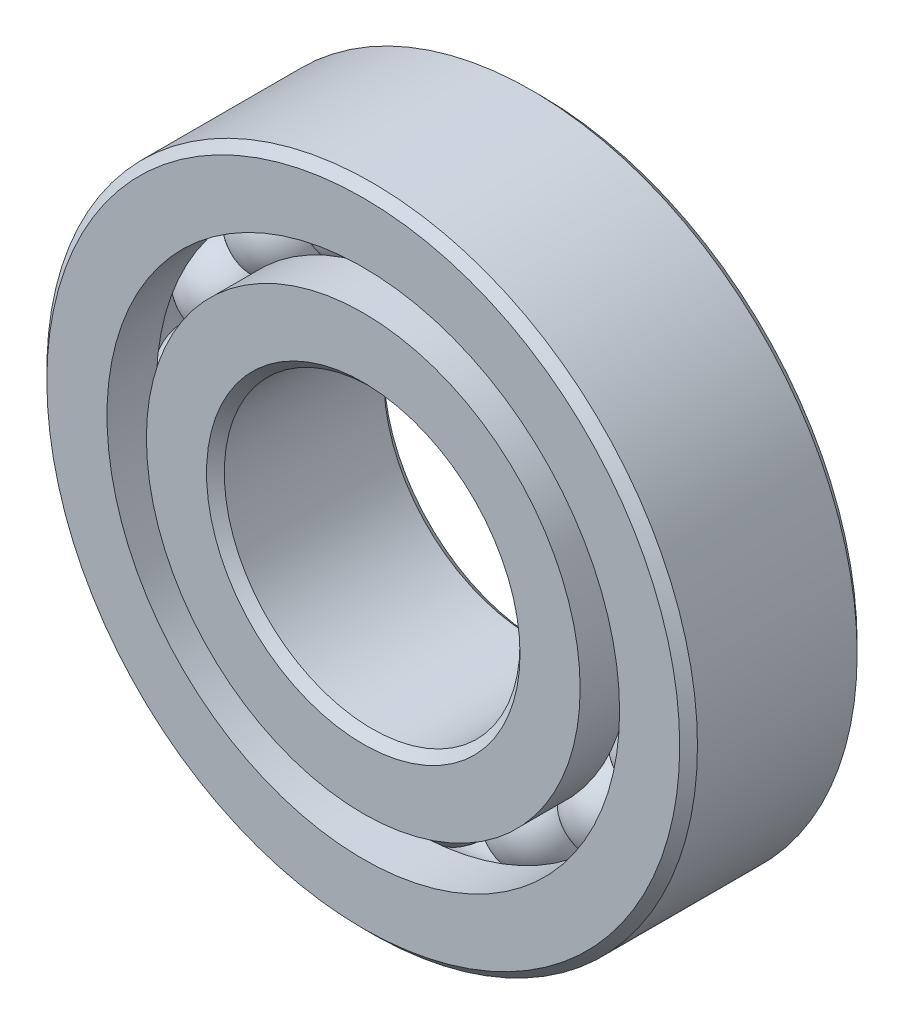
SolidWorks part; units mm, degrees
ref_plane "Front Plane" through (0, 0, 0) normal (0, 0, 1) x (1, 0, 0)
ref_plane "Top Plane" through (0, 0, 0) normal (0, 1, 0) x (1, 0, 0)
ref_plane "Right Plane" through (0, 0, 0) normal (1, 0, 0) x (0, 0, -1)
sketch "Sketch1" plane through (0, 0, 0) normal (1, 0, 0) x (0, 0, -1)
  line L0 (-1.5, 0) -> (1.5, 0) construction
  line L1 (0, 5.5) -> (0, -5.5) construction
  line L2 (1.35, 5.5) -> (-1.35, 5.5) construction
  line L3 (-1.35, 5.5) -> (-1.5, 5.35) construction
  line L4 (-1.5, 5.35) -> (-1.5, 4.3333) construction
  line L5 (-1.5, 4.3333) -> (-0.6667, 4.3333) construction
  line L6 (1.5, 4.3333) -> (0.6667, 4.3333) construction
  line L7 (1.5, 5.35) -> (1.5, 4.3333) construction
  line L8 (1.35, 5.5) -> (1.5, 5.35) construction
  line L9 (0, 5.5) -> (0, 4) construction
  line L10 (0, 4) -> (0, 2.5) construction
  arc A0 (-0.6667, 4.3333) -> (0.6667, 4.3333) centre (0, 4) cw construction
  arc A1 (-0.6667, 4.3333) -> (0.6667, 4.3333) centre (0, 4) ccw construction
  point P14 (0, 2.5)
  point P15 (0, -2.5)
  dimension "Width" = 3
  dimension "OD" = 11
  dimension "D1" = 45
  dimension "D2" = 0.15
  dimension "D3" = 1.3333
  dimension "Shaft Dia" = 5
  dimension "D4" = 0.3333
sketch "Sketch2" plane through (0, 0, 0) normal (1, 0, 0) x (0, 0, -1)
  line L0 (-1.5, 3.6667) -> (-0.6667, 3.6667)
  line L2 (-1.5, 3.6667) -> (-1.5, 2.65)
  line L3 (-1.5, 2.65) -> (-1.35, 2.5)
  line L4 (-1.35, 2.5) -> (1.35, 2.5)
  line L5 (0, 5.5) -> (0, -5.5) construction
  line L6 (0, 2.5) -> (0, 3.2546) construction
  line L7 (0, 3.2546) -> (0, 2.5) construction
  line L9 (-1.5, 5.35) -> (-1.5, 4.3333) construction
  line L10 (1.5, 3.6667) -> (0.6667, 3.6667)
  line L11 (1.5, 3.6667) -> (1.5, 2.65)
  line L12 (1.5, 2.65) -> (1.35, 2.5)
  line L13 (1.35, 5.5) -> (1.5, 5.35) construction
  line L14 (1.5, 5.35) -> (1.5, 4.3333) construction
  line L15 (1.5, 4.3333) -> (0.6667, 4.3333) construction
  line L16 (-1.5, 4.3333) -> (-0.6667, 4.3333) construction
  line L17 (1.35, 5.5) -> (-1.35, 5.5) construction
  line L18 (-1.35, 5.5) -> (-1.5, 5.35) construction
  line L19 (1.35, 5.5) -> (1.5, 5.35)
  line L20 (1.5, 5.35) -> (1.5, 4.3333)
  line L21 (1.5, 4.3333) -> (0.6667, 4.3333)
  line L22 (-1.5, 4.3333) -> (-0.6667, 4.3333)
  line L23 (-1.5, 5.35) -> (-1.5, 4.3333)
  line L24 (1.35, 5.5) -> (-1.35, 5.5)
  line L25 (-1.35, 5.5) -> (-1.5, 5.35)
  line L26 (-1.5, 2.65) -> (-1.35, 2.65) construction
  line L27 (-1.35, 2.65) -> (-1.35, 2.5) construction
  arc A0 (-0.6667, 3.6667) -> (0.6667, 3.6667) centre (0, 4) ccw
  arc A1 (0.6667, 4.3333) -> (-0.6667, 4.3333) centre (0, 4) ccw construction
  circle A2 centre (0, 4) radius 0.7454 construction
  arc A3 (-0.6667, 4.3333) -> (0.6667, 4.3333) centre (0, 4) cw
  dimension "D1" = 0.15
revolve "Revolve1" add sketch "Sketch2" angle 360 about L0
sketch "Sketch3" plane through (0, 0, 0) normal (1, 0, 0) x (0, 0, -1)
  line L0 (-0.7454, 4) -> (0.7454, 4)
  line L1 (0, 4) -> (0, 0) construction
  circle A1 centre (0, 4) radius 0.7454 construction
  arc A2 (-0.7454, 4) -> (0.7454, 4) centre (0, 4) cw
  arc A3 (0.6667, 4.3333) -> (-0.6667, 4.3333) centre (0, 4) ccw construction
  dimension "D1" = 1.4907
  dimension "D2" = 4
revolve "Revolve2" add sketch "Sketch3" angle 360 about L0
ref_axis "Axis1" through (0, 0, -1.5) along (0, 0, 1)
pattern_circular "CirPattern1" count 16 every 22.5 about axis through (0, 0, -1.5) along (0, 0, 1) of bodies 104
sketch "Sketch6" plane through (0, 0, 0) normal (0, 1, 0) x (1, 0, 0)
  point P0 (5.5, -1.5)
  point P1 (5.5, 1.5)
  dimension "D1" = 3
equation "\"D2@Sketch1\" = \"Width@Sketch1\"*.05"
equation "\"D3@Sketch1\" = \"Width@Sketch1\"/2.25"
equation "\"D4@Sketch1\" = \"D3@Sketch1\"/4"
equation "\"Balls@CirPattern1\"=\"D2@Sketch3\"*2*pi/\"D1@Sketch3\"-1"
equation "\"D2@CirPattern1\" = 360/\"Balls@CirPattern1\""
equation "\"D1@Sketch2\"=\"D2@Sketch1\""
equation "\"D1@Sketch6\"=\"Width@Sketch1\""
